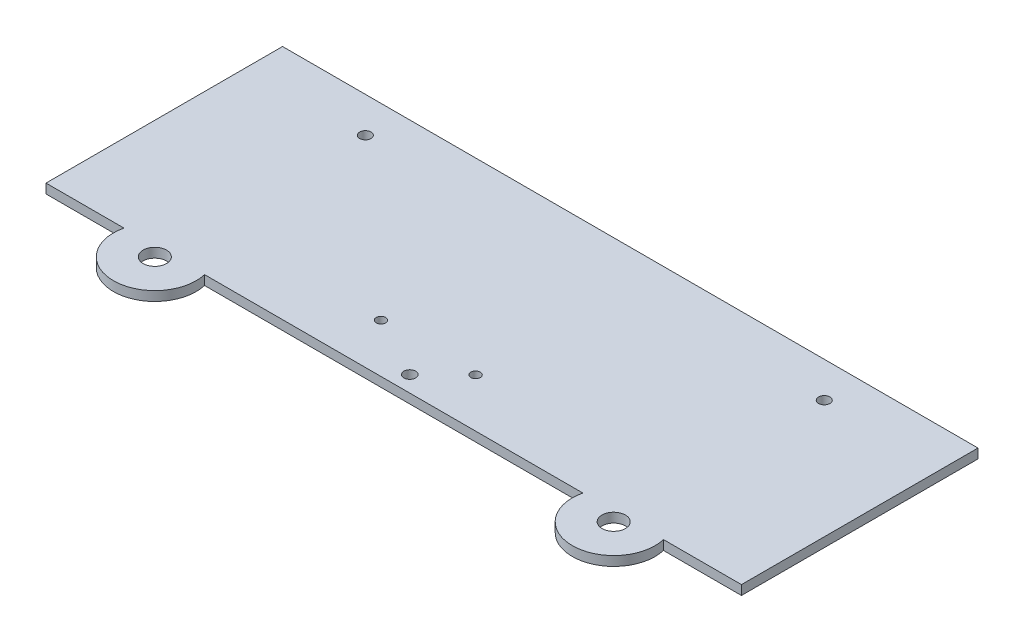
SolidWorks part; units mm, degrees
ref_plane "Front Plane" through (0, 0, 0) normal (0, 0, 1) x (1, 0, 0)
ref_plane "Top Plane" through (0, 0, 0) normal (0, 1, 0) x (1, 0, 0)
ref_plane "Right Plane" through (0, 0, 0) normal (1, 0, 0) x (0, 0, -1)
sketch "Sketch1" plane through (0, 0, 0) normal (0, 1, 0) x (1, 0, 0)
  line L0 (0, 0) -> (0, -63.5) construction
  line L1 (-186.69, -63.5) -> (186.69, -63.5)
  line L2 (-186.69, -63.5) -> (-186.69, 63.5)
  line L3 (-186.69, 63.5) -> (186.69, 63.5)
  line L4 (186.69, -63.5) -> (186.69, 63.5)
  line L5 (-186.69, -63.5) -> (186.69, 63.5) construction
  line L6 (-186.69, 63.5) -> (186.69, -63.5) construction
  line L7 (-123.19, -68.58) -> (-123.19, -63.5) construction
  line L8 (123.19, -68.58) -> (123.19, -63.5) construction
  line L9 (17.78, -37.338) -> (17.78, -63.5) construction
  circle A0 centre (-123.19, -68.58) radius 22.225
  circle A1 centre (123.19, -68.58) radius 22.225
  circle A2 centre (-123.19, -68.58) radius 6.2865
  circle A3 centre (123.19, -68.58) radius 6.2865
  circle A4 centre (-123.19, 44.45) radius 3.048
  circle A5 centre (123.19, 44.45) radius 3.048
  circle A6 centre (-33.02, -37.338) radius 2.54
  circle A7 centre (17.78, -37.338) radius 2.54
  circle A8 centre (0, -54.864) radius 3.175
  point P0 (0, 0)
  point P17 (123.19, 44.45)
  point P21 (-123.19, 44.45)
  point P24 (0, -54.864)
  dimension "D3" = 44.45
  dimension "D4" = 44.45
  dimension "D8" = 12.573
  dimension "D9" = 12.573
  dimension "D11" = 6.096
  dimension "D12" = 6.096
  dimension "D16" = 5.08
  dimension "D17" = 5.08
  dimension "D20" = 6.35
  dimension "D1" = 373.38
  dimension "D2" = 127
  dimension "D5" = 5.08
  dimension "D6" = 123.19
  dimension "D7" = 123.19
  dimension "D10" = 107.95
  dimension "D13" = 26.162
  dimension "D14" = 17.78
  dimension "D15" = 50.8
  dimension "D18" = 8.636
extrude "Boss-Extrude1" add sketch "Sketch1" along normal blind 5.0749 contours L1 A0 | L1 A1 | L3 L4 L1 L2 | A2 | A3 region at (-123.19, 0, 76.2008) region at (123.19, 0, 76.2008)
extrude "Cut-Extrude1" cut sketch "Sketch1<5>" along normal through all contours A3 | A2
sketch "Sketch1<5>" plane through (0, 0, 0) normal (0, 1, 0) x (1, 0, 0) same geometry as "Sketch1"
extrude "Cut-Extrude2" cut sketch "Sketch1<7>" along normal through all and the other way through all contours A4 | A5
sketch "Sketch1<7>" plane through (0, 0, 0) normal (0, 1, 0) x (1, 0, 0) same geometry as "Sketch1"
extrude "Cut-Extrude3" cut sketch "Sketch1<8>" along normal through all contours A7 | A6 | A8
sketch "Sketch1<8>" plane through (0, 0, 0) normal (0, 1, 0) x (1, 0, 0) same geometry as "Sketch1"
